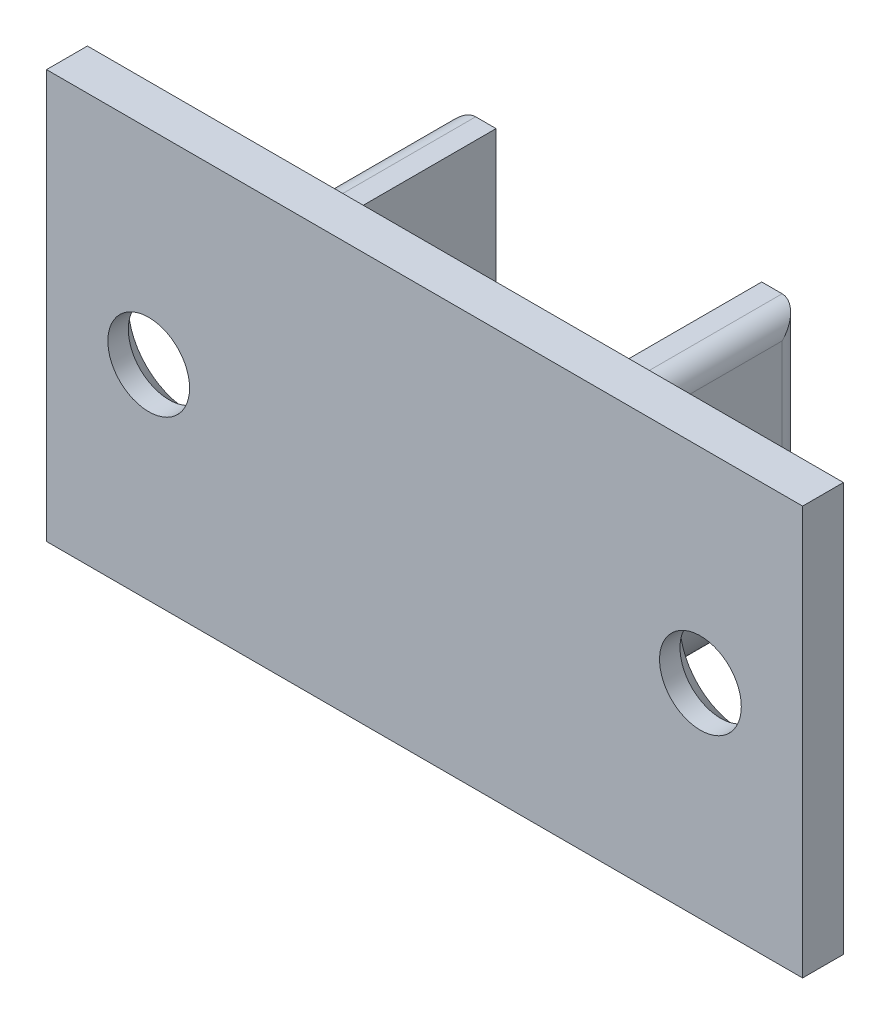
SolidWorks part; units mm, degrees
ref_plane "Plan de face" through (0, 0, 0) normal (0, 0, 1) x (1, 0, 0)
ref_plane "Plan de dessus" through (0, 0, 0) normal (0, 1, 0) x (1, 0, 0)
ref_plane "Plan de droite" through (0, 0, 0) normal (1, 0, 0) x (0, 0, -1)
sketch "Esquisse1" plane through (0, 0, 0) normal (0, 0, 1) x (1, 0, 0)
  line L0 (18.5, -991.781) -> (18.5, 49008.219) construction
  line L1 (0, 0) -> (37, 0)
  line L2 (0, 0) -> (0, 20)
  line L3 (0, 20) -> (37, 20)
  line L4 (37, 0) -> (37, 20)
  line L5 (-1000, 10) -> (49000, 10) construction
  line L6 (25, 10) -> (27, 10) construction
  line L7 (12, 10) -> (10, 10) construction
  line L8 (12, 10) -> (12, 18.5)
  line L9 (12, 18.5) -> (10, 18.5)
  line L10 (10, 10) -> (10, 18.5)
  line L11 (27, 10) -> (27, 18.5)
  line L12 (25, 18.5) -> (27, 18.5)
  line L13 (25, 10) -> (25, 18.5)
  circle A0 centre (5, 10) radius 2
  arc A1 (12, 10) -> (25, 10) centre (18.5, 10) ccw
  arc A2 (10, 10) -> (27, 10) centre (18.5, 10) ccw
  circle A3 centre (32, 10) radius 2
  point P10 (18.5, 20)
  point P12 (18.5, 10)
  point P18 (0, 10)
  dimension "D1" = 4
  dimension "D2" = 6.5
  dimension "D3" = 8.5
  dimension "D4" = 20
  dimension "D6" = 8.5
  dimension "D7" = 5
  dimension "D8" = 10
extrude "Boss.-Extru.3" add sketch "Esquisse1" along normal blind 2 contours L1 L4 L3 L2 A0 L11 L10 L9 L8 L13 L12 | L11 L12 L13 L8 L9 L10 region at (18.5, 10.1291, 0) region at (18.5, 3.2596, 0)
extrude "Boss.-Extru.4" add sketch "Esquisse1<5>" against normal blind 8 contours L11 L12 L13 L8 L9 L10 region at (18.5, 3.2596, 0)
sketch "Esquisse1<5>" plane through (0, 0, 0) normal (0, 0, 1) x (1, 0, 0) same geometry as "Esquisse1"
fillet "Congé3" radius 1 10 edges at (27, 14.25, -8) (10, 14.25, -8) (27, 14.25, 0) (27, 18.5, -4) (10, 18.5, -4) (11, 18.5, 0) (26, 18.5, 0) (10, 14.25, 0) (18.5, 1.5, 0) (18.5, 1.5, -8)
chamfer "Chanfrein2" distance 1 angle 45 2 edges at (7, 10, 0) (34, 10, 0)
